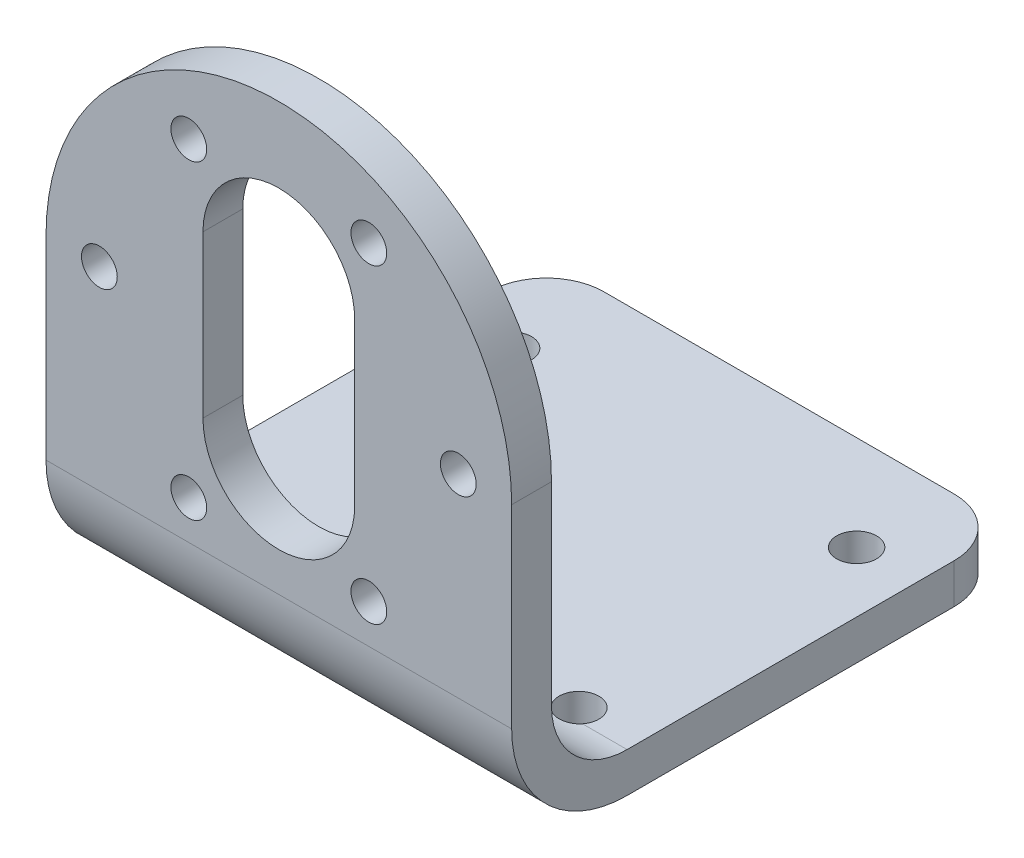
SolidWorks part; units mm, degrees
ref_plane "Front Plane" through (0, 0, 0) normal (0, 0, 1) x (1, 0, 0)
ref_plane "Top Plane" through (0, 0, 0) normal (0, 1, 0) x (1, 0, 0)
ref_plane "Right Plane" through (0, 0, 0) normal (1, 0, 0) x (0, 0, -1)
sketch "Sketch1" plane through (0, 0, 0) normal (0, 1, 0) x (1, 0, 0)
  line L1 (-47.1412, -7.433) -> (-6.7912, -7.433)
  line L2 (-47.1412, -7.433) -> (-47.1412, -50.783)
  line L3 (-47.1412, -50.783) -> (-6.7912, -50.783)
  line L4 (-6.7912, -7.433) -> (-6.7912, -50.783)
extrude "Boss-Extrude1" add sketch "Sketch1" along normal blind 47
sketch "Sketch3" plane through (0, 0, 50.783) normal (0, 0, 1) x (1, 0, 0)
  line L6 (-47.1412, 26.825) -> (-47.1412, 47)
  line L7 (-47.1412, 47) -> (-6.7912, 47)
  line L8 (-6.7912, 26.825) -> (-6.7912, 47)
  arc A1 (-6.7912, 26.825) -> (-47.1412, 26.825) centre (-26.9662, 26.825) ccw
  line M2 (-6.7912, 0) -> (-6.7912, 47)
  line M3 (-6.7912, 47) -> (-47.1412, 47)
  line M4 (-47.1412, 47) -> (-47.1412, 0)
extrude "Cut-Extrude2" cut sketch "Sketch3" against normal blind 102 contours A1 L7 M4 | A1 M2 M3 region at (-11.2977, 42.4936, 50.783) region at (-42.6348, 42.4936, 50.783)
fillet "Fillet1" radius 10 1 edges at (-26.9662, 0, 50.783)
sketch "Sketch5" plane through (-47.1412, 0, 0) normal (-1, 0, 0) x (0, 0, 1)
  line L0 (7.433, 0) -> (-6.6658, 0)
  line L1 (-6.6658, 0) -> (-6.6658, 3.45)
  line L2 (50.783, 47) -> (50.783, 59.7784)
  line L3 (50.783, 59.7784) -> (47.333, 59.7784)
  line L5 (-6.6658, 3.45) -> (36.5956, 3.45)
  line L6 (-6.6658, 3.45) -> (-6.6658, 59.7784)
  line L7 (-6.6658, 59.7784) -> (47.333, 59.7784)
  line L8 (47.333, 17.5785) -> (47.333, 59.7784)
  line L9 (36.5956, 3.45) -> (40.783, 3.45)
  line L12 (47.333, 10) -> (47.333, 17.5785)
  arc A1 (40.783, 3.45) -> (47.333, 10) centre (40.783, 10) ccw
  line M2 (50.783, 26.825) -> (7.433, 26.825)
  line M3 (7.433, 26.825) -> (7.433, 0)
extrude "Cut-Extrude3" cut sketch "Sketch5" against normal blind 102 contours L8 L7 L6 L5 M2 M3 | L5 L8 M2 M3 region at (-47.1412, 15.2394, 27.1987) region at (-47.1412, 38.9007, 17.2162)
fillet "Fillet2" radius 5 2 edges at (-6.7912, 1.725, 7.433) (-47.1412, 1.725, 7.433)
sketch "Sketch6" plane through (0, 3.45, 0) normal (0, 1, 0) x (1, 0, 0)
  line L0 (-27.9141, -7.433) -> (-27.9141, -13.933)
  line L1 (-42.1412, -7.433) -> (-11.7912, -7.433) construction
  line L2 (-47.1412, -24.2783) -> (-43.6412, -24.2783)
  line L3 (-47.1412, -12.433) -> (-47.1412, -40.783) construction
  line L4 (-6.7912, -25.5422) -> (-10.2912, -25.5422)
  line L5 (-6.7912, -12.433) -> (-6.7912, -40.783) construction
  line L6 (-43.6412, -24.2783) -> (-43.6412, -13.933)
  line L7 (-43.6412, -13.933) -> (-10.2912, -13.933)
  line L8 (-10.2912, -13.933) -> (-10.2912, -45.493)
  line L9 (-10.2912, -45.493) -> (-43.6412, -45.493)
  line L10 (-43.6412, -45.493) -> (-43.6412, -24.2783)
  line L11 (-41.9112, -17.393) -> (-41.9112, -37.993)
  line L12 (-12.0212, -17.393) -> (-12.0212, -37.993)
  circle A0 centre (-41.9112, -15.663) radius 1.73
  circle A1 centre (-12.0212, -15.663) radius 1.73
  circle A2 centre (-41.9112, -39.723) radius 1.73
  circle A3 centre (-12.0212, -39.723) radius 1.73
  point P24 (0, 0)
  line M12 (-47.1412, -40.783) -> (-6.7912, -40.783)
extrude "Cut-Extrude4" cut sketch "Sketch6" against normal blind 102 and the other way blind 102 contours A3 M12 | A3 M12 | A2 M12 | A2 M12 | A1 | A0 region at (-41.9112, 3.45, 15.663) region at (-41.9112, 3.45, 39.5133) region at (-41.9112, 3.45, 41.056) region at (-12.0212, 3.45, 15.663) region at (-12.0212, 3.45, 41.056) region at (-12.0212, 3.45, 39.5133)
sketch "Sketch7" plane through (0, 0, 50.783) normal (0, 0, 1) x (1, 0, 0)
  line L0 (-47.1412, 21.9829) -> (-33.5412, 21.9829)
  line L2 (-33.5412, 33.925) -> (-33.5412, 19.945)
  line L4 (-20.3912, 33.925) -> (-20.3912, 19.945)
  line L5 (-47.1412, 26.825) -> (-47.1412, 10) construction
  line L6 (-20.3912, 20.4169) -> (-6.7912, 20.4169)
  line L7 (-6.7912, 26.825) -> (-6.7912, 10) construction
  line L8 (-26.9662, 47) -> (-26.9662, 40.5)
  arc A0 (-6.7912, 26.825) -> (-47.1412, 26.825) centre (-26.9662, 26.825) ccw construction
  arc A1 (-20.3912, 33.925) -> (-33.5412, 33.925) centre (-26.9662, 33.925) ccw
  arc A2 (-33.5412, 19.945) -> (-20.3912, 19.945) centre (-26.9662, 19.945) ccw
extrude "Cut-Extrude5" cut sketch "Sketch7" against normal blind 102 contours L2 A2 L4 A1 region at (-26.9662, 26.935, 50.783)
sketch "Sketch8" plane through (0, 0, 50.783) normal (0, 0, 1) x (1, 0, 0)
  line L4 (-40.9662, 26.825) -> (-44.0662, 26.825)
  line L5 (-12.9662, 26.825) -> (-9.8662, 26.825)
  arc A0 (-33.8891, 38.9936) -> (-20.0433, 38.9936) centre (-26.9662, 26.825) ccw
  arc A1 (-35.5437, 41.6181) -> (-18.3887, 41.6181) centre (-26.9662, 26.825) ccw
  arc A2 (-20.0433, 14.6564) -> (-20.0519, 14.6448) centre (-26.9662, 19.725) cw
  arc A3 (-33.8806, 39.0052) -> (-33.8891, 38.9936) centre (-26.9662, 33.925) ccw
  circle A4 centre (-34.7662, 40.2772) radius 1.55
  circle A5 centre (-19.1662, 40.2772) radius 1.55
  circle A6 centre (-19.1662, 13.3728) radius 1.55
  arc A7 (-20.0433, 38.9936) -> (-20.0519, 39.0052) centre (-26.9662, 33.925) ccw
  circle A8 centre (-34.7662, 13.3728) radius 1.55
  arc A9 (-33.8806, 14.6448) -> (-33.8891, 14.6564) centre (-26.9662, 19.725) cw
  circle A10 centre (-42.5162, 26.825) radius 1.55
  circle A11 centre (-11.4162, 26.825) radius 1.55
extrude "Cut-Extrude6" cut sketch "Sketch8" against normal blind 102 contours A8 | A6 | L5 A11 | L5 A11 | L4 A10 | L4 A10 | A4 | A5 A4 region at (-42.5162, 26.1672, 50.783) region at (-42.5162, 27.4828, 50.783) region at (-34.7662, 40.2772, 50.783) region at (-34.7662, 13.3728, 50.783) region at (-19.1662, 13.3728, 50.783) region at (-11.4162, 26.1672, 50.783) region at (-11.4162, 27.4828, 50.783) region at (-19.1662, 40.2772, 50.783)
